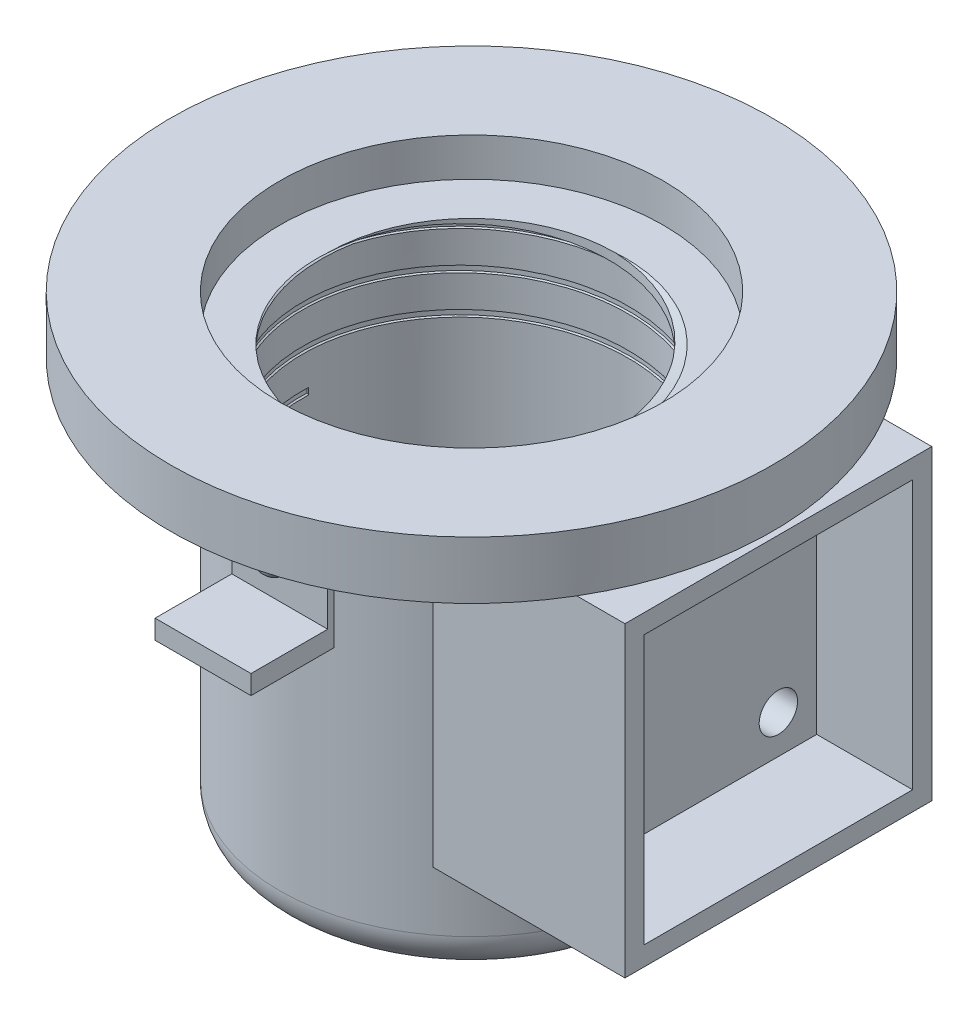
SolidWorks part; units mm, degrees
ref_plane "Front Plane" through (0, 0, 0) normal (0, 0, 1) x (1, 0, 0)
ref_plane "Top Plane" through (0, 0, 0) normal (0, 1, 0) x (1, 0, 0)
ref_plane "Right Plane" through (0, 0, 0) normal (1, 0, 0) x (0, 0, -1)
sketch "Sketch3" plane through (0, 0, 0) normal (0, 1, 0) x (1, 0, 0)
  circle A0 centre (0, 0) radius 10
extrude "Boss-Extrude3" add sketch "Sketch3" along normal blind 22
sketch "Sketch8" plane through (0, 22, 0) normal (0, 1, 0) x (1, 0, 0)
  circle A0 centre (0, 0) radius 8.5
extrude "Cut-Extrude2" cut sketch "Sketch8" against normal blind 22
sketch "Sketch14" plane through (0, 22, 0) normal (0, 1, 0) x (1, 0, 0)
  circle A0 centre (0, 0) radius 10
extrude "Cut-Extrude3" cut sketch "Sketch14" against normal blind 1
sketch "Sketch48" plane through (0, 21, 0) normal (0, 1, 0) x (1, 0, 0)
  line L1 (6, 8) -> (6, -8)
  line L5 (16, -8) -> (16, 8)
  line L8 (6, 8) -> (16, 8)
  line L9 (6, 8) -> (6, -8)
  line L10 (6, -8) -> (16, -8)
  line L11 (16, 8) -> (16, -8)
  circle A1 centre (0, 0) radius 10 construction
  circle M13 centre (0, 0) radius 10
extrude "Boss-Extrude20" add sketch "Sketch48" against normal blind 16 contours L10 L5 L8 M13 region at (12.3073, 21, 0)
sketch "Sketch17" plane through (16, 0, 0) normal (1, 0, 0) x (0, 0, -1)
  line L1 (-7, 20) -> (7, 20)
  line L25 (7, 20) -> (7, 6)
  line L27 (7, 6) -> (-7, 6)
  line L28 (7, 6) -> (7, 20)
  line L29 (7, 20) -> (-7, 20)
  line L30 (-7, 6) -> (-7, 20)
extrude "Cut-Extrude4" cut sketch "Sketch17" against normal blind 5 contours L28 L27 L30 L29
sketch "Sketch18" plane through (11, 0, 0) normal (1, 0, 0) x (0, 0, -1)
  circle A0 centre (5, 8) radius 1
extrude "Cut-Extrude5" cut sketch "Sketch18" against normal blind 10 contours A0 region at (11, 8, -5)
sketch "Sketch50" plane through (0, 21, 0) normal (0, 1, 0) x (1, 0, 0)
  line L0 (-2.5, 14) -> (2.5, 14)
  line L1 (2.5, 14) -> (2.5, 9.6825)
  line L3 (2.5, 9.6825) -> (-2.5, 9.6825)
  line L4 (-2.5, 9.6825) -> (-2.5, 14)
  arc A0 (6, 8) -> (6, -8) centre (0, 0) ccw construction
extrude "Boss-Extrude21" add sketch "Sketch50" against normal blind 7
sketch "Sketch52" plane through (2.5, 0, 0) normal (1, 0, 0) x (0, 0, -1)
  line L5 (10, 15) -> (14, 15)
  line L6 (10, 15) -> (10, 20)
  line L7 (10, 20) -> (14, 20)
  line L8 (14, 15) -> (14, 20)
extrude "Cut-Extrude13" cut sketch "Sketch52" against normal blind 5
sketch "Sketch53" plane through (0, 0, -10) normal (0, 0, -1) x (-1, 0, 0)
  circle A0 centre (0, 17.5) radius 1
extrude "Boss-Extrude22" add sketch "Sketch53" along normal blind 1
sketch "Sketch54" plane through (0, 21, 0) normal (0, 1, 0) x (1, 0, 0)
  line L0 (-2.5, 14) -> (-2.5, 9.6825)
  line L1 (2.5, -9.6825) -> (2.5, -14)
  line L2 (-2.5, -9.6825) -> (-2.5, -14)
  line L4 (2.5, -14) -> (-2.5, -14)
  line L5 (-2.5, -9.6825) -> (2.5, -9.6825)
  arc A0 (-2.5, 9.6825) -> (6, -8) centre (0, 0) ccw construction
  arc M12 (-2.5, 9.6825) -> (6, -8) centre (0, 0) ccw
extrude "Boss-Extrude23" add sketch "Sketch54" against normal blind 7 contours L4 L1 L2 M12 region at (0, 21, 11.9463)
sketch "Sketch57" plane through (2.5, 0, 0) normal (1, 0, 0) x (0, 0, -1)
  line L1 (-14, 14) -> (-14, 21) construction
  line L7 (-10, 15) -> (-14, 15)
  line L8 (-10, 15) -> (-10, 20)
  line L9 (-10, 20) -> (-14, 20)
  line L10 (-14, 15) -> (-14, 20)
extrude "Cut-Extrude14" cut sketch "Sketch57" against normal blind 5 contours L8 L7 L10 L9
sketch "Sketch58" plane through (0, 0, 10) normal (0, 0, 1) x (1, 0, 0)
  circle A0 centre (0, 17.5) radius 1
extrude "Boss-Extrude24" add sketch "Sketch58" along normal blind 1 contours A0
sketch "Sketch37" plane through (-2.5, 0, 0) normal (-1, 0, 0) x (0, 0, 1)
  line L0 (0, 0) -> (0, 4)
  line L1 (-10, 0) -> (10, 0) construction
  circle A0 centre (0, 4) radius 2
extrude "Cut-Extrude8" cut sketch "Sketch37" along normal blind 12.5 contours A0 region at (-2.5, 2.6258, 1.3742)
sketch "Sketch38" plane through (0, 21, 0) normal (0, 1, 0) x (1, 0, 0)
  circle A0 centre (0, 0) radius 15.6825
extrude "Boss-Extrude16" add sketch "Sketch38" along normal blind 3
sketch "Sketch39" plane through (0, 24, 0) normal (0, 1, 0) x (1, 0, 0)
  circle A0 centre (0, 0) radius 7.5
extrude "Cut-Extrude10" cut sketch "Sketch39" against normal blind 4 contours A0
thread "Thread2" pitch 2 method cut profile "Thread Profile4" start angle 0, offset 0, length 0, pitch 2, diameter 15
ref_plane "Plane10" through (-7.5, 24, 0) normal (0, 0, 1) x (-1, 0, 0)
sketch "Thread Profile4" plane through (-7.5, 24, 0) normal (0, 0, 1) x (-1, 0, 0)
  line L0 (0, 0) -> (0, 2) construction
  line L1 (0, 0) -> (1.0825, 0.625)
  line L2 (1.0825, 0.625) -> (1.0825, 0.875)
  line L3 (1.0825, 0.875) -> (0, 1.5)
  line L4 (1.0825, 0.75) -> (0, 0.75) construction
  line L11 (0, 0) -> (0, 1.5)
  point P2 (0, 0)
  dimension "Pitch" = 2
  dimension "Profile_Angle" = 60
  dimension "Profile_Land" = 0.25
  dimension "Profile_Height" = 1.0825
sketch "Sketch44" plane through (0, 24, 0) normal (0, 1, 0) x (1, 0, 0)
  circle A0 centre (0, 0) radius 10
extrude "Cut-Extrude11" cut sketch "Sketch44" against normal blind 2
fillet "Fillet1" radius 2 1 edges at (0, 0, 10)
fillet "Fillet2" radius 0.5 1 edges at (-1, 17.5, -11)
fillet "Fillet3" radius 0.5 1 edges at (1, 17.5, 11)
ref_axis "Axis1" through (0, 0, 0) along (0, 1, 0)
